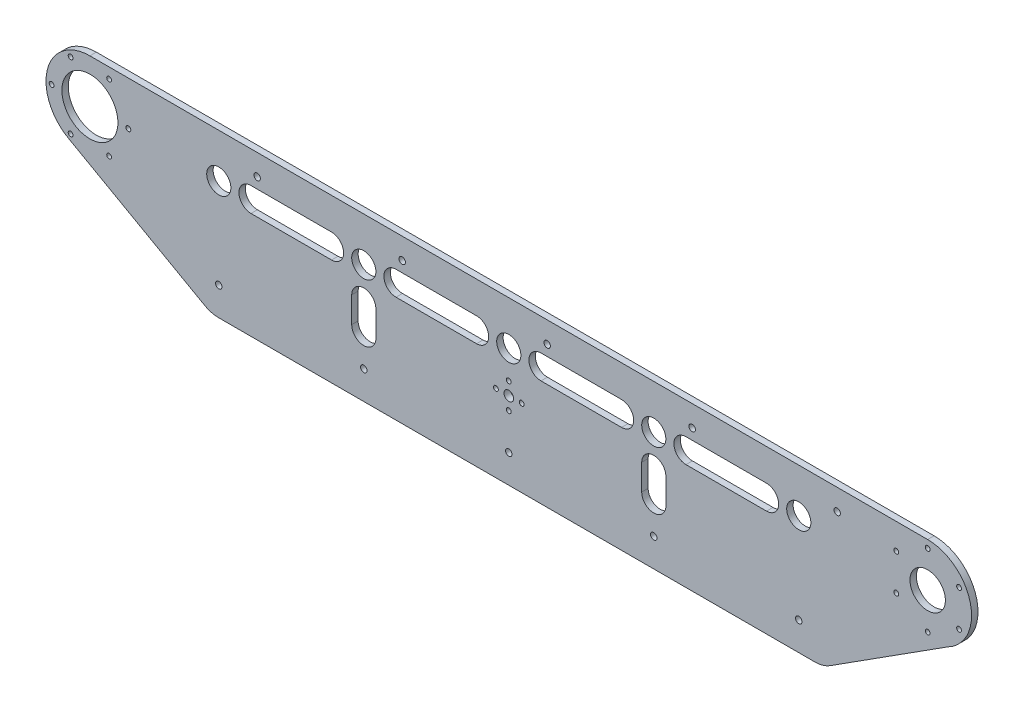
SolidWorks part; units mm, degrees
material "3.1305 (EN-AW 2117)"
ref_plane "Alzado" through (0, 0, 0) normal (0, 0, 1) x (1, 0, 0)
ref_plane "Planta" through (0, 0, 0) normal (0, 1, 0) x (1, 0, 0)
ref_plane "Vista lateral" through (0, 0, 0) normal (1, 0, 0) x (0, 0, -1)
sketch "Croquis1" plane through (0, 0, 0) normal (0, 0, 1) x (1, 0, 0)
  line L4 (102.5, 23.182) -> (90, 21.1607) construction
  line L5 (90, -23.8925) -> (180, -23.8925) construction
  line L6 (-102.5, -9.9669) -> (-83.0991, -6.8298) construction
  line L7 (-215.9366, -23.8925) -> (-260, -23.8925) construction
  line L8 (-90, -23.8925) -> (-92, -23.8925) construction
  line L9 (-188.6184, -23.8925) -> (-182, -23.8925) construction
  line L10 (-260, -23.8925) -> (-260, 1.2874) construction
  line L11 (-179.1956, -41.4802) -> (179.1956, -41.4802)
  line L12 (-260, 32.1075) -> (-180, -23.8925) construction
  line L18 (179.1956, -41.4802) -> (190.0108, -41.4802)
  line L19 (0, -23.8925) -> (-12.5, -23.8925) construction
  line L20 (-180, -23.8925) -> (-167.5, -23.8925) construction
  line L21 (-90, -23.8925) -> (-92, -23.8925) construction
  line L24 (-90, -23.8925) -> (-90, 32.1075) construction
  line L28 (-182, -23.9062) -> (-188.6184, -23.8925) construction
  line L30 (-180, -23.8925) -> (-196.3846, -12.4232) construction
  line L31 (-196.3846, -12.4232) -> (-221.6689, 5.2758) construction
  line L32 (-260, 32.1075) -> (-243.6154, 20.6383) construction
  line L36 (-272.7427, 8.0318) -> (-188.6256, -39.2409)
  line L41 (-90, 32.1075) -> (-90, 12.1075) construction
  line L42 (-90, -23.8925) -> (-90, -3.8925) construction
  line L43 (-82.5, 12.1075) -> (-82.5, -3.8925)
  line L44 (-97.5, 12.1075) -> (-97.5, -3.8925)
  line L45 (-90, 44.6075) -> (-90, -11.3925) construction
  line L46 (-20, 24.6075) -> (-70, 24.6075)
  line L47 (-20, 39.6075) -> (-70, 39.6075)
  line L48 (287.24, 32.1075) -> (284.0739, 32.1075) construction
  line L50 (260, 59.3475) -> (260, 32.1075) construction
  line L51 (90, 44.6075) -> (90, -11.3925) construction
  line L52 (90, -23.8925) -> (90, -3.8925) construction
  line L53 (90, 32.1075) -> (90, 12.1075) construction
  line L54 (260, 32.1075) -> (260, 39.1075) construction
  line L56 (-260, 4.1) -> (-260, 32.1075) construction
  line L59 (20, 39.6075) -> (70, 39.6075)
  line L60 (260, 32.1075) -> (260, 25.1075) construction
  line L65 (-160, 39.6075) -> (-110, 39.6075)
  line L66 (-160, 24.6075) -> (-110, 24.6075)
  line L83 (-260, 59.3475) -> (260, 59.3475)
  line L87 (-287.24, 32.1075) -> (-284.0739, 32.1075) construction
  line L89 (160, 24.6075) -> (110, 24.6075)
  line L91 (-167.5, -23.8925) -> (-180, -23.8925) construction
  line L92 (-102.5, 23.182) -> (-90, 21.1607) construction
  line L93 (160, 39.6075) -> (110, 39.6075)
  line L94 (-6.5, 6.6075) -> (-141.7981, 6.6075) construction
  line L95 (90, -23.8925) -> (88, -23.8925) construction
  line L96 (-135, 39.6075) -> (-135, 14.7545) construction
  line L97 (135, 39.6075) -> (135, 20.6383) construction
  line L98 (-88, -23.8925) -> (-90, -23.8925) construction
  line L100 (-83.0991, -6.8298) -> (-102.5, -9.9669) construction
  line L101 (-90, 21.1607) -> (-102.5, 23.182) construction
  line L103 (83.0991, -6.8298) -> (102.5, -9.9669) construction
  line L106 (90, 21.1607) -> (102.5, 23.182) construction
  line L115 (90, -23.8925) -> (90, 32.1075) construction
  line L116 (90, -23.8925) -> (92, -23.8925) construction
  line L119 (265.4417, 3.373) -> (265.4184, 3.7892) construction
  line L121 (90, -23.8925) -> (92, -23.8925) construction
  line L122 (102.5, -9.9669) -> (83.0991, -6.8298) construction
  line L124 (20, 24.6075) -> (70, 24.6075)
  line L125 (97.5, 12.1075) -> (97.5, -3.8925)
  line L126 (82.5, 12.1075) -> (82.5, -3.8925)
  line L127 (272.7427, 8.0318) -> (199.4836, -38.7153)
  circle A5 centre (0, -23.8925) radius 2
  circle A6 centre (-90, -23.8925) radius 2
  circle A7 centre (-180, -23.8925) radius 2
  circle A25 centre (-90, 32.1075) radius 7.5
  arc A26 (-82.5, 12.1075) -> (-97.5, 12.1075) centre (-90, 12.1075) ccw
  arc A27 (-97.5, -3.8925) -> (-82.5, -3.8925) centre (-90, -3.8925) ccw
  arc A28 (-20, 39.6075) -> (-20, 24.6075) centre (-20, 32.1075) cw
  arc A29 (-70, 24.6075) -> (-70, 39.6075) centre (-70, 32.1075) cw
  circle A30 centre (0, 32.1075) radius 7.5
  circle A51 centre (-260, 32.1075) radius 17.4
  arc A52 (-260, 59.3475) -> (-272.7427, 8.0318) centre (-260, 32.1075) ccw
  arc A54 (-188.6256, -39.2409) -> (-179.1956, -41.4802) centre (-180, -23.8925) ccw
  arc A56 (260, 59.3475) -> (272.7427, 8.0318) centre (260, 32.1075) cw
  circle A57 centre (260, 32.1075) radius 11
  arc A58 (70, 24.6075) -> (70, 39.6075) centre (70, 32.1075) ccw
  arc A59 (20, 39.6075) -> (20, 24.6075) centre (20, 32.1075) ccw
  arc A60 (97.5, -3.8925) -> (82.5, -3.8925) centre (90, -3.8925) cw
  arc A61 (82.5, 12.1075) -> (97.5, 12.1075) centre (90, 12.1075) cw
  circle A62 centre (90, 32.1075) radius 7.5
  circle A66 centre (90, -23.8925) radius 2
  arc A71 (-160, 39.6075) -> (-160, 24.6075) centre (-160, 32.1075) ccw
  arc A72 (-110, 24.6075) -> (-110, 39.6075) centre (-110, 32.1075) ccw
  arc A73 (160, 39.6075) -> (160, 24.6075) centre (160, 32.1075) cw
  arc A74 (110, 24.6075) -> (110, 39.6075) centre (110, 32.1075) cw
  circle A75 centre (-180, 32.1075) radius 7.5
  circle A76 centre (180, 32.1075) radius 7.5
  circle A77 centre (-8, 6.6075) radius 1.5
  circle A78 centre (0, 14.6075) radius 1.5
  circle A79 centre (8, 6.6075) radius 1.5
  circle A80 centre (0, -1.3925) radius 1.5
  circle A81 centre (0, 6.6075) radius 3
  circle A82 centre (180, -23.8925) radius 2
  arc A83 (199.4836, -38.7153) -> (190.0108, -41.4802) centre (190.0108, -23.8702) cw
  point P0 (0, 6.6075)
  dimension "D5" = 4
  dimension "D7" = 4
  dimension "D9" = 4
  dimension "D11" = 22
  dimension "D10" = 54.48
  dimension "D12" = 27.24
  dimension "D15" = 7
  dimension "D16" = 7
  dimension "D18" = 4
  dimension "D20" = 6
  dimension "D21" = 34.8
  dimension "D23" = 4
  dimension "D24" = 90
  dimension "D25" = 15
  dimension "D28" = 15
  dimension "D30" = 15
  dimension "D31" = 15
  dimension "D33" = 17.61
  dimension "D17" = 3
  dimension "D32" = 4
  dimension "D4" = 30.5
  dimension "D6" = 90
  dimension "D8" = 90
  dimension "D13" = 80
  dimension "D14" = 56
  dimension "D19" = 20
  dimension "D22" = 20
  dimension "D26" = 20
  dimension "D27" = 56
  dimension "D29" = 20
extrude "Saliente-Extruir1" add sketch "Croquis1" along normal mid plane 4
sketch "Croquis2" plane through (0, 0, 2) normal (0, 0, 1) x (1, 0, 0)
  line L0 (-287.24, 32.1075) -> (-283.74, 32.1075) construction
  line L1 (-260, 32.1075) -> (-271.95, 52.8055) construction
  line L2 (-260, 32.1075) -> (-248.05, 52.8055) construction
  line L3 (-260, 32.1075) -> (-271.95, 11.4095) construction
  line L4 (-260, 32.1075) -> (-248.05, 11.4095) construction
  line L5 (-260, 32.1075) -> (-236.1, 32.1075) construction
  line L6 (-260, 32.1075) -> (-283.74, 32.1075) construction
  arc A0 (-260, 59.3475) -> (-272.7427, 8.0318) centre (-260, 32.1075) ccw construction
  circle A1 centre (-283.74, 32.1075) radius 1.5
  circle A3 centre (-271.95, 52.8055) radius 1.5
  circle A4 centre (-248.05, 52.8055) radius 1.5
  circle A5 centre (-236.1, 32.1075) radius 1.5
  circle A6 centre (-248.05, 11.4095) radius 1.5
  circle A7 centre (-271.95, 11.4095) radius 1.5
  dimension "D2" = 3
  dimension "D12" = 3
  dimension "D13" = 3
  dimension "D14" = 3
  dimension "D15" = 3
  dimension "D16" = 3
  dimension "D1" = 3.5
  dimension "D3" = 60
  dimension "D4" = 60
  dimension "D5" = 60
  dimension "D6" = 60
  dimension "D7" = 23.9
  dimension "D8" = 23.9
  dimension "D9" = 23.9
  dimension "D10" = 23.9
  dimension "D11" = 23.9
extrude "Cortar-Extruir1" cut sketch "Croquis2" against normal blind 10
sketch "Croquis3" plane through (0, 0, 2) normal (0, 0, 1) x (1, 0, 0)
  line L0 (260, 32.1075) -> (260, 54.6075) construction
  circle A0 centre (260, 54.6075) radius 1.5
  circle A1 centre (279.4856, 43.3575) radius 1.5
  circle A2 centre (279.4856, 20.8575) radius 1.5
  circle A3 centre (260, 9.6075) radius 1.5
  circle A4 centre (240.5144, 20.8575) radius 1.5
  circle A5 centre (240.5144, 43.3575) radius 1.5
  dimension "D2" = 3
  dimension "D1" = 22.5
  dimension "D3" = 6
extrude "Cortar-Extruir2" cut sketch "Croquis3" against normal blind 10
sketch "Croquis4" plane through (0, 0, 2) normal (0, 0, 1) x (1, 0, 0)
  line L0 (240.5144, 43.3575) -> (240.5144, 46.2175) construction
  line L1 (-156.1656, 44.2175) -> (-156.1656, 46.2175) construction
  line L2 (-156.1656, 46.2175) -> (-66.1656, 46.2175) construction
  line L3 (-66.1656, 46.2175) -> (23.8344, 46.2175) construction
  line L4 (23.8344, 46.2175) -> (113.8344, 46.2175) construction
  line L5 (113.8344, 46.2175) -> (203.8344, 46.2175) construction
  line L6 (240.5144, 46.2175) -> (203.8344, 46.2175) construction
  circle A0 centre (-156.1656, 46.2175) radius 2
  circle A1 centre (-66.1656, 46.2175) radius 2
  circle A2 centre (23.8344, 46.2175) radius 2
  circle A3 centre (113.8344, 46.2175) radius 2
  circle A4 centre (203.8344, 46.2175) radius 2
  dimension "D3" = 4
  dimension "D8" = 4
  dimension "D9" = 4
  dimension "D10" = 4
  dimension "D11" = 4
  dimension "D2" = 2.86
  dimension "D4" = 90
  dimension "D5" = 90
  dimension "D6" = 90
  dimension "D7" = 90
  dimension "D12" = 36.68
extrude "Cortar-Extruir3" cut sketch "Croquis4" against normal blind 10
